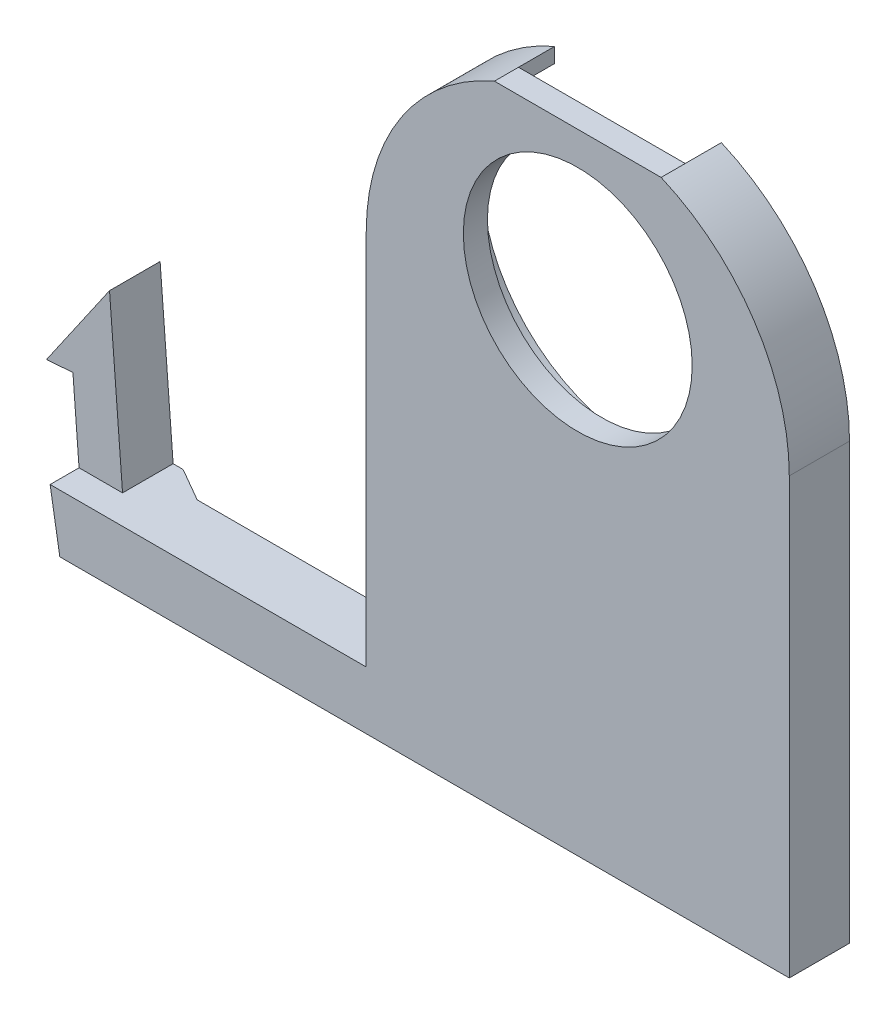
SolidWorks part; units mm, degrees
ref_plane "Front Plane" through (0, 0, 0) normal (0, 0, 1) x (1, 0, 0)
ref_plane "Top Plane" through (0, 0, 0) normal (0, 1, 0) x (1, 0, 0)
ref_plane "Right Plane" through (0, 0, 0) normal (1, 0, 0) x (0, 0, -1)
sketch "Sketch1" plane through (0, 0, 0) normal (0, 0, 1) x (1, 0, 0)
  line L0 (5.32, 14.0026) -> (5.32, 14.6195)
  line L1 (0, 0) -> (17.56, 0)
  line L2 (0, 0) -> (0, 6.55)
  line L3 (0, 6.55) -> (17.56, 6.55)
  line L4 (17.56, 0) -> (17.56, 6.55)
  line L6 (12.24, 14.0026) -> (12.24, 14.6195)
  arc A0 (5.32, 14.6195) -> (0, 6.55) centre (8.78, 6.55) ccw
  arc A1 (5.32, 14.0026) -> (12.24, 14.0026) centre (8.78, 8.5) ccw
  arc A2 (17.56, 6.55) -> (12.24, 14.6195) centre (8.78, 6.55) ccw
  dimension "D4" = 13
  dimension "D1" = 17.56
  dimension "D2" = 6.55
  dimension "D5" = 1.95
  dimension "D6" = 5.32
extrude "Boss-Extrude1" add sketch "Sketch1" along normal blind 1.5 contours A1 L3 L2 L1 L4 | A1 L0 A0 L3 | L3 A2 L6 A1 region at (1.98, 9.9073, 0) region at (8.78, 1.8126, 0) region at (15.58, 9.9073, 0)
sketch "Sketch3" plane through (0, 0, 1.5) normal (0, 0, 1) x (1, 0, 0)
  line L5 (5.32, 14.0026) -> (5.32, 14.6195)
  line L6 (0, 6.55) -> (0, 0)
  line L7 (0, 0) -> (17.56, 0)
  line L8 (17.56, 0) -> (17.56, 6.55)
  line L9 (12.24, 14.6195) -> (12.24, 14.0026)
  line L10 (5.32, 14.0026) -> (5.32, 14.6195)
  line L11 (0, 6.55) -> (0, 0)
  line L12 (0, 0) -> (17.56, 0)
  line L13 (17.56, 0) -> (17.56, 6.55)
  line L14 (12.24, 14.6195) -> (12.24, 14.0026)
  line L15 (0, 0) -> (17.56, 0)
  line L16 (17.56, 6.55) -> (17.56, 0)
  line L17 (0, 0) -> (0, 6.55)
  line L18 (5.32, 14.6195) -> (12.24, 14.6195)
  arc A3 (5.32, 14.0026) -> (12.24, 14.0026) centre (8.78, 8.5) ccw
  arc A4 (5.32, 14.6195) -> (0, 6.55) centre (8.78, 6.55) ccw
  arc A5 (17.56, 6.55) -> (12.24, 14.6195) centre (8.78, 6.55) ccw
  arc A6 (5.32, 14.0026) -> (12.24, 14.0026) centre (8.78, 8.5) ccw
  arc A7 (5.32, 14.6195) -> (0, 6.55) centre (8.78, 6.55) ccw
  arc A8 (17.56, 6.55) -> (12.24, 14.6195) centre (8.78, 6.55) ccw
  arc A9 (17.56, 6.55) -> (12.24, 14.6195) centre (8.78, 6.55) ccw
  arc A10 (0, 6.55) -> (5.32, 14.6195) centre (8.78, 6.55) cw
  arc M9 (12.24, 14.0026) -> (5.32, 14.0026) centre (8.78, 8.5) cw
  line M10 (5.32, 14.0026) -> (5.32, 14.6195)
  arc M11 (5.32, 14.6195) -> (0, 6.55) centre (8.78, 6.55) ccw
  line M12 (0, 6.55) -> (0, 0)
  line M13 (0, 0) -> (17.56, 0)
  line M14 (17.56, 0) -> (17.56, 6.55)
  arc M15 (17.56, 6.55) -> (12.24, 14.6195) centre (8.78, 6.55) ccw
  line M16 (12.24, 14.6195) -> (12.24, 14.0026)
  dimension "D1" = 0
extrude "Boss-Extrude2" add sketch "Sketch3" along normal blind 1 contours M16 M9 M10 M11 M12 M13 M14 M15 | L18 M10 M9 M16 region at (8.78, 1.7715, 1.5) region at (8.78, 8.4788, 1.5)
sketch "Sketch4" plane through (0, 0, 1.5) normal (0, 0, -1) x (-1, 0, 0)
  circle A0 centre (-8.78, 8.5) radius 4.75
  dimension "D1" = 9.5
extrude "Cut-Extrude1" cut sketch "Sketch4" against normal through all
sketch "Sketch5" plane through (0, 0, 0) normal (0, -1, 0) x (1, 0, 0)
  line L1 (0, 2.5) -> (17.56, 2.5)
  line L2 (0, 2.5) -> (0, 0)
  line L3 (0, 0) -> (17.56, 0)
  line L4 (17.56, 2.5) -> (17.56, 0)
extrude "Boss-Extrude3" add sketch "Sketch5" along normal blind 0.15
sketch "Sketch6" plane through (0, -0.15, 0) normal (0, -1, 0) x (1, 0, 0)
  line L4 (0, 2.5) -> (0, 0)
  line L5 (0, 0) -> (17.56, 0)
  line L6 (17.56, 0) -> (17.56, 2.5)
  line L7 (17.56, 2.5) -> (0, 2.5)
  line L8 (0, 2.5) -> (0, 0)
  line L9 (0, 0) -> (17.56, 0)
  line L10 (17.56, 0) -> (17.56, 2.5)
  line L11 (17.56, 2.5) -> (0, 2.5)
  dimension "D1" = 0
extrude "Boss-Extrude4" add sketch "Sketch6" along normal blind 11.35
sketch "Sketch7" plane through (0, 0, 0) normal (-1, 0, 0) x (0, 0, 1)
  line L0 (2.5, 6.55) -> (2.5, -11.5) construction
  line L1 (0, -11.5) -> (2.5, -11.5)
  line L2 (0, -11.5) -> (0, -9.1)
  line L3 (0, -9.1) -> (2.5, -9.1)
  line L4 (2.5, -11.5) -> (2.5, -9.1)
  dimension "D1" = 2.4
extrude "Boss-Extrude5" add sketch "Sketch7" along normal blind 12.72
sketch "Sketch8" plane through (0, 0, 0) normal (0, 0, -1) x (-1, 0, 0)
  line L0 (13.1212, -9.1) -> (13.376, -5.8)
  line L1 (13.376, -5.8) -> (14.4727, -5.8847)
  line L2 (14.4727, -5.8847) -> (11.8563, -2.1)
  line L3 (11.8563, -2.1) -> (11.3158, -9.1)
  line L4 (12.72, -9.1) -> (0, -9.1) construction
  line L5 (13.1212, -9.1) -> (12.72, -11.5)
  line L6 (12.72, -11.5) -> (12.72, -9.1)
  line L7 (12.72, -9.1) -> (11.3158, -9.1)
  dimension "D1" = 3.3
  dimension "D3" = 2.9
  dimension "D4" = 1.8
extrude "Boss-Extrude6" add sketch "Sketch8" against normal blind 1.3 and the other way blind 0.8
sketch "Sketch9" plane through (0, 0, 0) normal (0, 0, -1) x (-1, 0, 0)
  line L1 (11.3158, -9.1) -> (12.72, -9.1)
  line L2 (11.3158, -9.1) -> (11.3158, -11.5)
  line L3 (11.3158, -11.5) -> (12.72, -11.5)
  line L4 (12.72, -9.1) -> (12.72, -11.5)
extrude "Boss-Extrude7" add sketch "Sketch9" along normal up to surface (0.8 mm away) up to face at (-12.7974, -7.5121, -0.8)
chamfer "Chamfer3" distance 1.8 angle 30 1 edges at (-11.3158, -10.3, 0) first distance on face at (4.7608, 1.8737, 0)
sketch "Sketch10" plane through (0, 0, 1.3) normal (0, 0, 1) x (1, 0, 0)
  line L0 (-12.72, -11.5) -> (-12.72, -9.1)
  line L1 (-12.72, -9.1) -> (-13.1212, -9.1)
  line L2 (-13.1212, -9.1) -> (-12.72, -11.5)
extrude "Boss-Extrude8" add sketch "Sketch10" along normal up to surface (1.2 mm away) up to face at (4.03, 8.5, 2.5)
